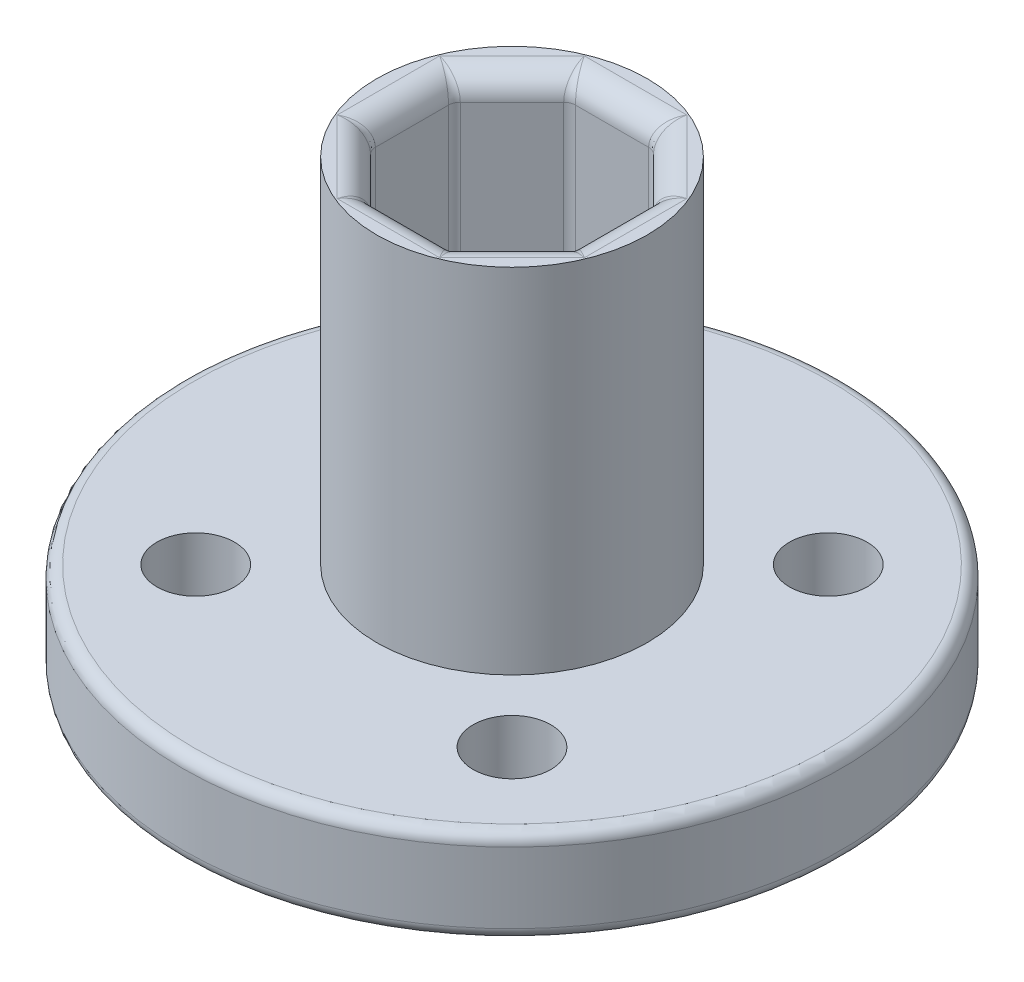
SolidWorks part; units mm, degrees
ref_plane "Front Plane" through (0, 0, 0) normal (0, 0, 1) x (1, 0, 0)
ref_plane "Top Plane" through (0, 0, 0) normal (0, 1, 0) x (1, 0, 0)
ref_plane "Right Plane" through (0, 0, 0) normal (1, 0, 0) x (0, 0, -1)
sketch "Sketch1" plane through (0, 0, 0) normal (0, 1, 0) x (1, 0, 0)
  circle A0 centre (0, 0) radius 14
  dimension "D1" = 28
extrude "Boss-Extrude1" add sketch "Sketch1" along normal blind 4 contours A0
sketch "Sketch3" plane through (0, 4, 0) normal (0, 1, 0) x (1, 0, 0)
  circle A0 centre (0, 0) radius 5.75
  dimension "D1" = 11.5
extrude "Boss-Extrude2" add sketch "Sketch3" along normal blind 15
sketch "Sketch6" plane through (0, 19, 0) normal (0, 1, 0) x (1, 0, 0)
  line L1 (1.7604, 4.25) -> (-1.7604, 4.25)
  line L2 (-1.7604, 4.25) -> (-4.25, 1.7604)
  line L3 (-4.25, 1.7604) -> (-4.25, -1.7604)
  line L4 (-4.25, -1.7604) -> (-1.7604, -4.25)
  line L5 (-1.7604, -4.25) -> (1.7604, -4.25)
  line L6 (1.7604, -4.25) -> (4.25, -1.7604)
  line L7 (4.25, -1.7604) -> (4.25, 1.7604)
  line L8 (4.25, 1.7604) -> (1.7604, 4.25)
  circle A0 centre (0, 0) radius 4.25 construction
  dimension "D1" = 8.5
extrude "Cut-Extrude3" cut sketch "Sketch6" against normal through all
sketch "Sketch5" plane through (0, 0, 0) normal (0, -1, 0) x (1, 0, 0)
  line L1 (-6.7175, -6.7175) -> (6.7175, -6.7175) construction
  line L2 (-6.7175, -6.7175) -> (-6.7175, 6.7175) construction
  line L3 (-6.7175, 6.7175) -> (6.7175, 6.7175) construction
  line L4 (6.7175, -6.7175) -> (6.7175, 6.7175) construction
  line L5 (-6.7175, -6.7175) -> (6.7175, 6.7175) construction
  line L6 (-6.7175, 6.7175) -> (6.7175, -6.7175) construction
  circle A0 centre (6.7175, 6.7175) radius 1.65
  circle A1 centre (-6.7175, 6.7175) radius 1.65
  circle A2 centre (-6.7175, -6.7175) radius 1.65
  circle A3 centre (6.7175, -6.7175) radius 1.65
  point P0 (0, 0)
  dimension "D2" = 3.3
  dimension "D1" = 9.5
extrude "Cut-Extrude2" cut sketch "Sketch5" against normal through all
chamfer "Chamfer1" distance 1.6 angle 45 4 edges at (6.7175, 0, -8.3675) (-6.7175, 0, -8.3675) (6.7175, 0, 5.0675) (-6.7175, 0, 5.0675)
fillet "Fillet1" radius 1 8 edges at (0, 19, 4.25) (-3.0052, 19, 3.0052) (-4.25, 19, 0) (-3.0052, 19, -3.0052) (0, 19, -4.25) (3.0052, 19, -3.0052) (4.25, 19, 0) (3.0052, 19, 3.0052)
fillet "Fillet2" radius 0.5 18 edges at (0, 0, 14) (0, 4, 14) (-1.7604, 9, -4.25) (-4.25, 9, -1.7604) (-4.25, 9, 1.7604) (-1.7604, 9, 4.25) (1.7604, 9, 4.25) (4.25, 9, 1.7604) (4.25, 9, -1.7604) (1.7604, 9, -4.25) (-1.8817, 18.7071, -4.5429) (-4.5429, 18.7071, -1.8817) (-4.5429, 18.7071, 1.8817) (-1.8817, 18.7071, 4.5429) (1.8817, 18.7071, 4.5429) (4.5429, 18.7071, 1.8817) (4.5429, 18.7071, -1.8817) (1.8817, 18.7071, -4.5429)
